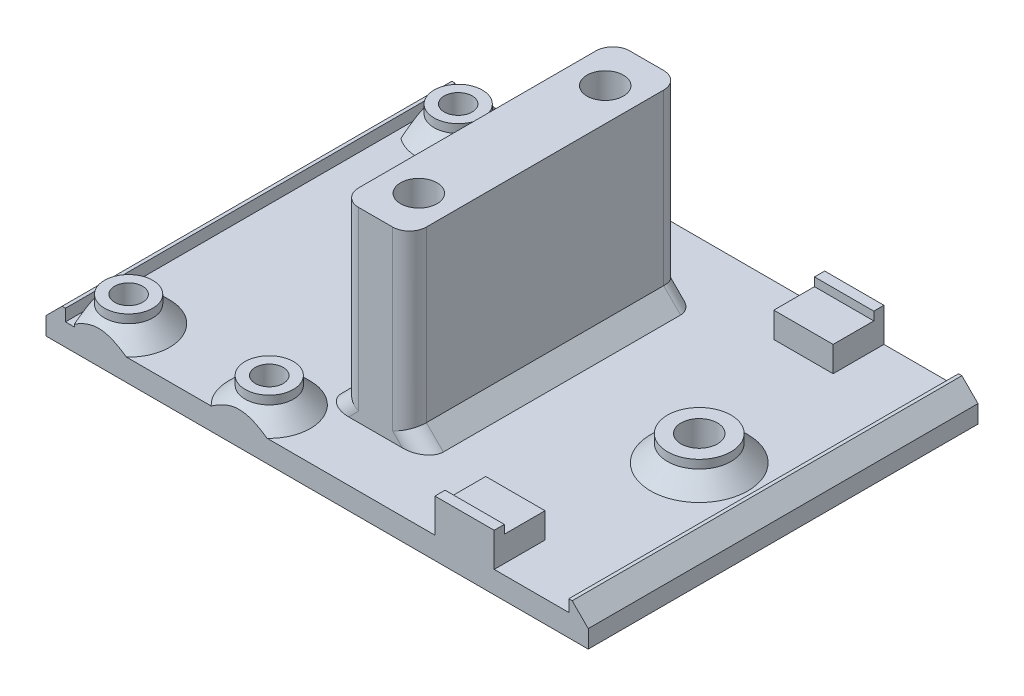
SolidWorks part; units mm, degrees
ref_plane "Płaszczyzna przednia" through (0, 0, 0) normal (0, 0, 1) x (1, 0, 0)
ref_plane "Płaszczyzna górna" through (0, 0, 0) normal (0, 1, 0) x (1, 0, 0)
ref_plane "Płaszczyzna prawa" through (0, 0, 0) normal (1, 0, 0) x (0, 0, -1)
sketch "Sketch1" plane through (0, 0, 0) normal (0, 1, 0) x (1, 0, 0)
  line L1 (0, 0) -> (64, 0)
  line L2 (0, 0) -> (0, 46)
  line L3 (0, 46) -> (64, 46)
  line L4 (64, 0) -> (64, 46)
  dimension "D1" = 46
  dimension "64" = 64
extrude "Boss-Extrude1" add sketch "Sketch1" along normal blind 2.6
hole_wizard "Ø3.3 (3.3) Diameter Hole1" positions "Sketch2" profile "Sketch3" hole size "Ø3.3" standard "DIN" end condition through all
sketch "Sketch2" plane through (0, 2.6, 0) normal (0, 1, 0) x (1, 0, 0)
  point P0 (22.8, 42.45)
  point P3 (6.2, 42.45)
  point P6 (6.2, 3.55)
  point P9 (22.8, 3.55)
sketch "Sketch3" plane through (22.8, 2.6, -42.45) normal (1, 0, 0) x (0, 0, 1)
  line L0 (0, 0) -> (0, 2.6)
  line L1 (0, 2.6) -> (1.65, 2.6)
  line L2 (1.65, 2.6) -> (1.65, 0)
  line L5 (1.65, 0) -> (0, 0)
  line L11 (0, -6.35) -> (0, 107.95) construction
  dimension "Thru Hole Dia." = 3.3
  dimension "Thru Hole Depth" = 2.6
sketch "Sketch4" plane through (0, 2.6, 0) normal (0, 1, 0) x (1, 0, 0)
  circle A0 centre (6.2, 3.55) radius 1.65 construction
  circle A1 centre (22.8, 3.55) radius 1.65 construction
  circle A2 centre (22.8, 42.45) radius 1.65 construction
  circle A3 centre (6.2, 42.45) radius 1.65 construction
  circle A4 centre (6.2, 3.55) radius 1.65
  circle A5 centre (22.8, 3.55) radius 1.65
  circle A6 centre (22.8, 42.45) radius 1.65
  circle A7 centre (6.2, 42.45) radius 1.65
  circle A8 centre (6.2, 42.45) radius 2.85
  circle A9 centre (22.8, 42.45) radius 2.85
  circle A10 centre (22.8, 3.55) radius 2.85
  circle A11 centre (6.2, 3.55) radius 2.85
  dimension "D1" = 1.2
extrude "Boss-Extrude2" add sketch "Sketch4" along normal blind 3
chamfer "Chamfer1" distance 2 angle 45 4 edges at (22.8, 2.6, -6.4) (6.2, 2.6, -6.4) (22.8, 2.6, -45.3) (6.2, 2.6, -45.3)
sketch "Sketch6" plane through (0, 2.6, 0) normal (0, 1, 0) x (1, 0, 0)
  line L1 (3.35, 46) -> (0, 46)
  line L2 (3.35, 46) -> (3.35, 0)
  line L3 (3.35, 0) -> (0, 0)
  line L4 (0, 46) -> (0, 0)
  circle A0 centre (6.2, 3.55) radius 2.85 construction
  circle A1 centre (6.2, 42.45) radius 2.85 construction
  circle A2 centre (6.2, 3.55) radius 2.85
  circle A3 centre (6.2, 42.45) radius 2.85
  arc M8 (9.5045, 46) -> (2.8955, 46) centre (6.2, 42.45) cw
  arc M12 (2.8955, 0) -> (9.5045, 0) centre (6.2, 3.55) cw
extrude "Cut-Extrude2" cut sketch "Sketch6" along normal through all contours A3 L2 L1 M8 | A2 L2 L3 M12 region at (2.5286, 2.6, -42.4201) region at (2.5286, 2.6, -3.5799)
hole_wizard "Ø4.3 (4.3) Diameter Hole1" positions "Sketch7" profile "Sketch8" hole size "Ø4.3" standard "DIN" end condition through all
sketch "Sketch7" plane through (0, 2.6, 0) normal (0, 1, 0) x (1, 0, 0)
  point P0 (54.1, 23)
sketch "Sketch8" plane through (54.1, 2.6, -23) normal (1, 0, 0) x (0, 0, 1)
  line L0 (0, 0) -> (0, 2.6)
  line L1 (0, 2.6) -> (2.15, 2.6)
  line L2 (2.15, 2.6) -> (2.15, 0)
  line L5 (2.15, 0) -> (0, 0)
  line L11 (0, -6.35) -> (0, 107.95) construction
  dimension "Thru Hole Dia." = 4.3
  dimension "Thru Hole Depth" = 2.6
sketch "Sketch9" plane through (0, 2.6, 0) normal (0, 1, 0) x (1, 0, 0)
  circle A0 centre (54.1, 23) radius 2.15 construction
  circle A1 centre (54.1, 23) radius 2.15
  circle A2 centre (54.1, 23) radius 3.75
  dimension "D1" = 1.6
extrude "Boss-Extrude3" add sketch "Sketch9" along normal up to surface (3 mm away) up to face at (22.8, 5.6, -39.6)
chamfer "Chamfer2" distance 2 angle 45 1 edges at (54.1, 2.6, -26.75)
sketch "Sketch10" plane through (0, 2.6, 0) normal (0, 1, 0) x (1, 0, 0)
  line L0 (64, 46) -> (26.1045, 46) construction
  line L1 (52.9, 46) -> (45.9, 46)
  line L2 (52.9, 46) -> (52.9, 40)
  line L3 (52.9, 40) -> (45.9, 40)
  line L4 (45.9, 46) -> (45.9, 40)
  line L5 (26.1045, 0) -> (64, 0) construction
  line L6 (45.9, 0) -> (52.9, 0)
  line L7 (45.9, 0) -> (45.9, 6)
  line L8 (45.9, 6) -> (52.9, 6)
  line L9 (52.9, 0) -> (52.9, 6)
  line L10 (58.05, 44.5) -> (52.9, 44.5) construction
  line L11 (58.05, 28.9) -> (58.05, 47.1) construction
  line L12 (58.05, 44.5) -> (40.75, 44.5) construction
  line L14 (45.9, 42.389) -> (40.75, 42.389) construction
  line L15 (40.75, 47.1) -> (40.75, 28.9) construction
  dimension "D1" = 6
  dimension "D2" = 7
extrude "Boss-Extrude4" add sketch "Sketch10" along normal up to surface (3 mm away) up to face at (54.1, 5.6, -20.85)
sketch "Sketch11" plane through (0, 5.6, 0) normal (0, 1, 0) x (1, 0, 0)
  line L1 (52.9, 46) -> (45.9, 46)
  line L2 (52.9, 46) -> (52.9, 44.8)
  line L3 (52.9, 44.8) -> (45.9, 44.8)
  line L4 (45.9, 46) -> (45.9, 44.8)
  line L6 (45.9, 46) -> (45.9, 40) construction
  line L8 (45.9, 6) -> (45.9, 0) construction
  line L9 (52.9, 0) -> (45.9, 0)
  line L10 (52.9, 0) -> (52.9, 1.2)
  line L11 (52.9, 1.2) -> (45.9, 1.2)
  line L12 (45.9, 0) -> (45.9, 1.2)
  dimension "D1" = 1.2
  dimension "D2" = 1.2
extrude "Boss-Extrude5" add sketch "Sketch11" along normal blind 1
sketch "Sketch12" plane through (0, 2.6, 0) normal (0, 1, 0) x (1, 0, 0)
  line L0 (38.8, 29.3894) -> (35.9, 29.3894) construction
  line L1 (35.9, 39) -> (27.9, 39)
  line L2 (35.9, 39) -> (35.9, 7)
  line L3 (35.9, 7) -> (27.9, 7)
  line L4 (27.9, 39) -> (27.9, 7)
  line L5 (38.8, 44.5) -> (38.8, 1.5) construction
  line L6 (30.2552, 46) -> (30.2552, 39) construction
  line L7 (27.9, 31.5368) -> (25, 31.5368) construction
  line L8 (25, 1.5) -> (25, 44.5) construction
  line L9 (45.9, 46) -> (26.1045, 46) construction
  line L11 (30.2552, 7) -> (30.2552, 0) construction
  line L12 (26.1045, 0) -> (45.9, 0) construction
  dimension "D1" = 32
  dimension "10" = 8
extrude "Boss-Extrude6" add sketch "Sketch12" along normal up to surface (22 mm away) contours L1 L4 L3 L2 up to face at (54.1, 2.6, -28.75)
chamfer "Chamfer3" distance 2 angle 45 2 edges at (35.9, 2.6, -23) (27.9, 2.6, -23)
fillet "Fillet1" radius 2 8 edges at (27.9, 14.6, -39) (35.9, 14.6, -39) (27.9, 14.6, -7) (35.9, 14.6, -7) (26.9632, 3.6632, -39) (36.9, 3.6, -39) (26.9632, 3.6632, -7) (36.9, 3.6, -7)
hole_wizard "Ø4.3 (4.3) Diameter Hole2" positions "Sketch13" profile "Sketch15" hole size "Ø4.3" standard "DIN"
sketch "Sketch13" plane through (0, 24.6, 0) normal (0, 1, 0) x (1, 0, 0)
  point P0 (32, 34)
  point P3 (32, 12)
  point P7 (0, 0)
  point P8 (0, 0)
sketch "Sketch15" plane through (32, 24.6, -34) normal (1, 0, 0) x (0, 0, 1)
  line L0 (0, 0) -> (0, 13.2919)
  line L1 (0, 13.2919) -> (2.15, 12)
  line L2 (2.15, 12) -> (2.15, 0)
  line L5 (2.15, 0) -> (0, 0)
  line L10 (0, 13.2919) -> (-2.15, 12) construction
  line L11 (0, -6.35) -> (0, 107.95) construction
  dimension "Hole Dia." = 4.3
  dimension "Hole Depth" = 12
  dimension "Drill Angle" = 118
sketch "Sketch17" plane through (0, 2.6, 0) normal (0, 1, 0) x (1, 0, 0)
  line L0 (0, 0) -> (3.35, 0) construction
  line L1 (0, 46) -> (2.3, 46)
  line L2 (0, 46) -> (0, 0)
  line L3 (0, 0) -> (2.3, 0)
  line L4 (2.3, 46) -> (2.3, 0)
  line L5 (64, 46) -> (52.9, 46) construction
  line L6 (64, 0) -> (61.7, 0)
  line L7 (64, 0) -> (64, 46)
  line L8 (64, 46) -> (61.7, 46)
  line L9 (61.7, 0) -> (61.7, 46)
  dimension "D1" = 2.3
extrude "Boss-Extrude7" add sketch "Sketch17" along normal blind 2
chamfer "Chamfer4" distance 2.5 angle 45 2 edges at (64, 4.6, -23) (0, 4.6, -23)
sketch "Sketch19" plane through (0, 0, 0) normal (0, 0, 1) x (1, 0, 0)
  line L1 (2.3, 4.4) -> (-5.2481, 4.4)
  line L2 (2.3, 4.4) -> (2.3, 4)
  line L3 (2.3, 4) -> (-5.2481, 4)
  line L4 (-5.2481, 4.4) -> (-5.2481, 4)
  line L5 (61.7, 4.4) -> (75.0626, 4.4)
  line L6 (61.7, 4.4) -> (61.7, 4)
  line L7 (61.7, 4) -> (75.0626, 4)
  line L8 (75.0626, 4.4) -> (75.0626, 4)
  dimension "D1" = 0.4
extrude "Cut-Extrude3" cut sketch "Sketch19" against normal through all
hole_wizard "Ø4.3 (4.3) Diameter Hole3" positions "Sketch20" profile "Sketch21" hole size "Ø4.3" standard "DIN"
sketch "Sketch20" plane through (0, 0, 0) normal (0, -1, 0) x (-1, 0, 0)
  line L8 (-29.9, 39) -> (-33.9, 39)
  line L9 (-27.9, 9) -> (-27.9, 37)
  line L10 (-33.9, 7) -> (-29.9, 7)
  line L11 (-35.9, 37) -> (-35.9, 9)
  line L12 (-29.9, 39) -> (-33.9, 39)
  line L13 (-27.9, 9) -> (-27.9, 37)
  line L14 (-33.9, 7) -> (-29.9, 7)
  line L15 (-35.9, 37) -> (-35.9, 9)
  line L16 (-32, 12) -> (-32, 18) construction
  line L17 (-32, 28) -> (-32, 34) construction
  arc A8 (-27.9, 37) -> (-29.9, 39) centre (-29.9, 37) ccw
  arc A9 (-29.9, 7) -> (-27.9, 9) centre (-29.9, 9) ccw
  arc A10 (-35.9, 9) -> (-33.9, 7) centre (-33.9, 9) ccw
  arc A11 (-33.9, 39) -> (-35.9, 37) centre (-33.9, 37) ccw
  arc A12 (-27.9, 37) -> (-29.9, 39) centre (-29.9, 37) ccw
  arc A13 (-29.9, 7) -> (-27.9, 9) centre (-29.9, 9) ccw
  arc A14 (-35.9, 9) -> (-33.9, 7) centre (-33.9, 9) ccw
  arc A15 (-33.9, 39) -> (-35.9, 37) centre (-33.9, 37) ccw
  circle A16 centre (-32, 12) radius 2.15 construction
  circle A17 centre (-32, 34) radius 2.15 construction
  circle A18 centre (-32, 12) radius 2.15
  circle A19 centre (-32, 34) radius 2.15
  point P0 (-32, 28)
  point P2 (-32, 18)
  dimension "D2" = 10
  dimension "D1" = 0
sketch "Sketch21" plane through (32, 0, -28) normal (1, 0, 0) x (0, 0, -1)
  line L0 (0, 0) -> (0, 13.2919)
  line L1 (0, 13.2919) -> (2.15, 12)
  line L2 (2.15, 12) -> (2.15, 0)
  line L5 (2.15, 0) -> (0, 0)
  line L10 (0, 13.2919) -> (-2.15, 12) construction
  line L11 (0, -6.35) -> (0, 107.95) construction
  dimension "Hole Dia." = 4.3
  dimension "Hole Depth" = 12
  dimension "Drill Angle" = 118
